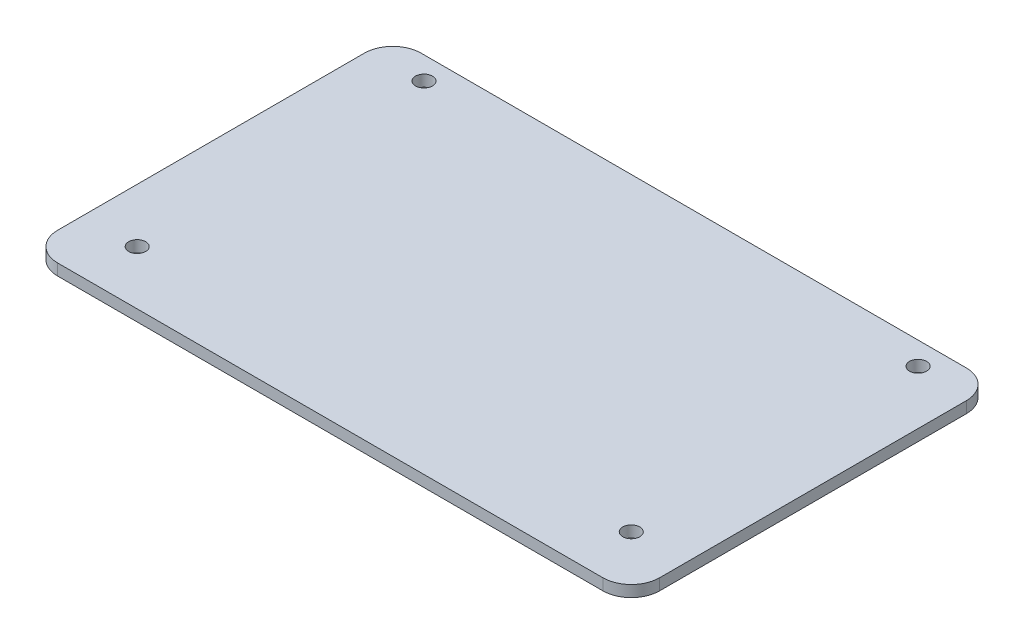
SolidWorks part; units mm, degrees
ref_plane "Front Plane" through (0, 0, 0) normal (0, 0, 1) x (1, 0, 0)
ref_plane "Top Plane" through (0, 0, 0) normal (0, 1, 0) x (1, 0, 0)
ref_plane "Right Plane" through (0, 0, 0) normal (1, 0, 0) x (0, 0, -1)
sketch "Sketch1" plane through (0, 0, 0) normal (0, 1, 0) x (1, 0, 0)
  line L1 (-53, -32) -> (53, -32)
  line L2 (-53, -32) -> (-53, 32)
  line L3 (-53, 32) -> (53, 32)
  line L4 (53, -32) -> (53, 32)
  line L5 (-53, -32) -> (53, 32) construction
  line L6 (-53, 32) -> (53, -32) construction
  point P0 (0, 0)
  dimension "D1" = 106
  dimension "D2" = 64
extrude "Boss-Extrude1" add sketch "Sketch1" along normal blind 2
fillet "Fillet1" radius 5 4 edges at (-53, 1, -32) (-53, 1, 32) (53, 1, -32) (53, 1, 32)
sketch "Sketch2" plane through (0, 2, 0) normal (0, 1, 0) x (1, 0, 0)
  line L0 (-53, 27) -> (-53, -27) construction
  line L1 (48, 32) -> (-48, 32) construction
  line L2 (-48, -32) -> (48, -32) construction
  line L3 (0, -1.1) -> (0, 1.1) construction
  circle A0 centre (-43.5, 28) radius 1.5
  circle A1 centre (-43.5, -22.5) radius 1.5
  circle A2 centre (43.5, -22.5) radius 1.5
  circle A3 centre (43.5, 28) radius 1.5
  dimension "D1" = 3
  dimension "D4" = 3
  dimension "D2" = 9.5
  dimension "D3" = 4
  dimension "D5" = 9.5
  dimension "D6" = 9.5
extrude "Cut-Extrude1" cut sketch "Sketch2" against normal up to surface (2 mm away) up to face at (0, 0, 0)
sketch "Sketch3" plane through (0, 2, 0) normal (0, 1, 0) x (1, 0, 0)
  line L0 (0, -1.1) -> (0, 1.1) construction
  circle A0 centre (-43.5, 28) radius 3.5
  circle A1 centre (-43.5, -22.5) radius 3.5
  circle A2 centre (43.5, -22.5) radius 3.5
  circle A3 centre (43.5, 28) radius 3.5
  dimension "D1" = 7
  dimension "D2" = 7
